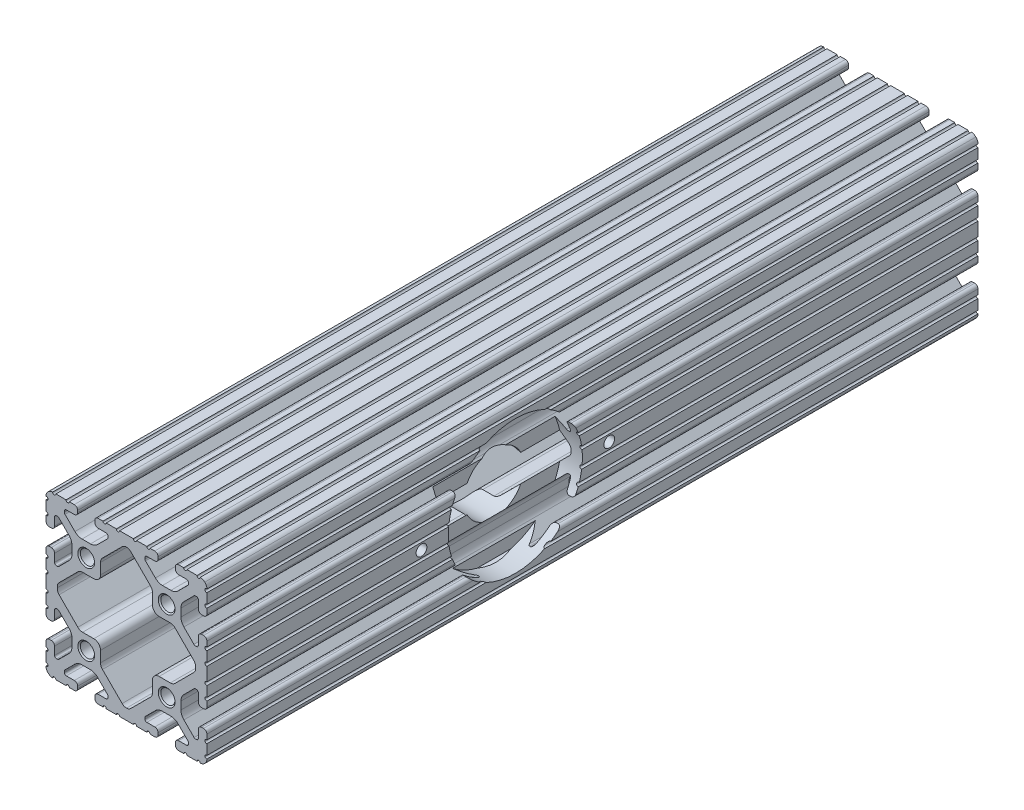
SolidWorks part; units mm, degrees
material "6061-T6 (SS)"
ref_plane "Front Plane" through (0, 0, 0) normal (0, 0, 1) x (1, 0, 0)
ref_plane "Top Plane" through (0, 0, 0) normal (0, 1, 0) x (1, 0, 0)
ref_plane "Right Plane" through (0, 0, 0) normal (1, 0, 0) x (0, 0, -1)
ref_plane "Plane1" through (0, 0, -254) normal (0, 0, -1) x (-1, 0, 0)
sketch "Sketch1" plane through (0, 0, -254) normal (0, 0, -1) x (-1, 0, 0)
  line L0 (31.9021, -2.4756) -> (23.0141, -11.3637)
  line L1 (20.769, -12.2936) -> (15.4686, -12.2936)
  line L2 (12.2936, -15.4686) -> (12.2936, -20.5983)
  line L3 (11.3637, -22.8433) -> (2.0515, -32.1555)
  line L4 (-2.0515, -32.1555) -> (-11.3637, -22.8433)
  line L5 (-12.2936, -20.5983) -> (-12.2936, -15.4686)
  line L6 (-15.4686, -12.2936) -> (-20.769, -12.2936)
  line L7 (-23.0141, -11.3637) -> (-31.9021, -2.4756)
  line L8 (-31.9021, 2.4756) -> (-23.0141, 11.3637)
  line L9 (-20.769, 12.2936) -> (-15.4686, 12.2936)
  line L10 (-12.2936, 15.4686) -> (-12.2936, 20.5983)
  line L11 (-11.3637, 22.8433) -> (-2.0515, 32.1555)
  line L12 (2.0515, 32.1555) -> (11.3637, 22.8433)
  line L13 (12.2936, 20.5983) -> (12.2936, 15.4686)
  line L14 (15.4686, 12.2936) -> (20.769, 12.2936)
  line L15 (23.0141, 11.3637) -> (31.9021, 2.4756)
  line L16 (36.5252, -23.0554) -> (35.6108, -23.0554)
  line L17 (34.036, -24.6302) -> (34.036, -28.448)
  line L18 (33.147, -29.337) -> (32.6643, -29.337)
  line L19 (32.0357, -29.0766) -> (27.1976, -24.2385)
  line L20 (25.8064, -20.8799) -> (25.8064, -17.2201)
  line L21 (27.1976, -13.8615) -> (31.9489, -9.1101)
  line L22 (32.7869, -8.763) -> (33.0603, -8.763)
  line L23 (34.036, -9.7387) -> (34.036, -13.4698)
  line L24 (35.6108, -15.0446) -> (36.5252, -15.0446)
  line L25 (38.1, -13.4698) -> (38.1, -11.075)
  line L26 (38.1, -9.552) -> (38.1, -4.7238)
  line L27 (38.1, -3.2007) -> (38.1, 3.2007)
  line L28 (38.1, 4.7238) -> (38.1, 9.552)
  line L29 (38.1, 11.075) -> (38.1, 13.4698)
  line L30 (36.5252, 15.0446) -> (35.6108, 15.0446)
  line L31 (34.036, 13.4698) -> (34.036, 9.7387)
  line L32 (33.0603, 8.763) -> (32.7869, 8.763)
  line L33 (31.9489, 9.1101) -> (27.1976, 13.8615)
  line L34 (25.8064, 17.2201) -> (25.8064, 20.8799)
  line L35 (27.1976, 24.2385) -> (32.0357, 29.0766)
  line L36 (32.6643, 29.337) -> (33.147, 29.337)
  line L37 (34.036, 28.448) -> (34.036, 24.6302)
  line L38 (35.6108, 23.0554) -> (36.5252, 23.0554)
  line L39 (38.1, 24.6302) -> (38.1, 27.0238)
  line L40 (38.1, 28.5453) -> (38.1, 33.373)
  line L41 (33.4288, 38.1) -> (28.6011, 38.1)
  line L42 (27.0772, 38.1) -> (24.6888, 38.1)
  line L43 (23.114, 36.5252) -> (23.114, 35.6108)
  line L44 (24.6888, 34.036) -> (28.448, 34.036)
  line L45 (29.337, 33.147) -> (29.337, 32.7207)
  line L46 (29.1002, 31.8885) -> (24.4093, 27.1976)
  line L47 (21.0507, 25.8064) -> (17.0493, 25.8064)
  line L48 (13.6907, 27.1976) -> (9.0234, 31.8649)
  line L49 (8.763, 32.4935) -> (8.763, 33.147)
  line L50 (9.652, 34.036) -> (13.4112, 34.036)
  line L51 (14.986, 35.6108) -> (14.986, 36.5252)
  line L52 (13.4112, 38.1) -> (11.1289, 38.1)
  line L53 (9.6053, 38.1) -> (4.7773, 38.1)
  line L54 (3.2537, 38.1) -> (-3.2537, 38.1)
  line L55 (-4.7773, 38.1) -> (-9.6053, 38.1)
  line L56 (-11.1289, 38.1) -> (-13.4112, 38.1)
  line L57 (-14.986, 36.5252) -> (-14.986, 35.6108)
  line L58 (-13.4112, 34.036) -> (-9.652, 34.036)
  line L59 (-8.763, 33.147) -> (-8.763, 32.4935)
  line L60 (-9.0234, 31.8649) -> (-13.6907, 27.1976)
  line L61 (-17.0493, 25.8064) -> (-21.0507, 25.8064)
  line L62 (-24.4093, 27.1976) -> (-29.1002, 31.8885)
  line L63 (-29.337, 32.7207) -> (-29.337, 33.147)
  line L64 (-28.448, 34.036) -> (-24.6888, 34.036)
  line L65 (-23.114, 35.6108) -> (-23.114, 36.5252)
  line L66 (-24.6888, 38.1) -> (-27.0772, 38.1)
  line L67 (-28.6011, 38.1) -> (-33.4288, 38.1)
  line L68 (-38.1, 33.373) -> (-38.1, 28.5453)
  line L69 (-38.1, 27.0238) -> (-38.1, 24.6302)
  line L70 (-36.5252, 23.0554) -> (-35.6108, 23.0554)
  line L71 (-34.036, 24.6302) -> (-34.036, 28.448)
  line L72 (-33.147, 29.337) -> (-32.6643, 29.337)
  line L73 (-32.0357, 29.0766) -> (-27.1976, 24.2385)
  line L74 (-25.8064, 20.8799) -> (-25.8064, 17.2201)
  line L75 (-27.1976, 13.8615) -> (-31.9489, 9.1101)
  line L76 (-32.7869, 8.763) -> (-33.0603, 8.763)
  line L77 (-34.036, 9.7387) -> (-34.036, 13.4698)
  line L78 (-35.6108, 15.0446) -> (-36.5252, 15.0446)
  line L79 (-38.1, 13.4698) -> (-38.1, 11.075)
  line L80 (-38.1, 9.552) -> (-38.1, 4.7238)
  line L81 (-38.1, 3.2007) -> (-38.1, -3.2007)
  line L82 (-38.1, -4.7238) -> (-38.1, -9.552)
  line L83 (-38.1, -11.075) -> (-38.1, -13.4698)
  line L84 (-36.5252, -15.0446) -> (-35.6108, -15.0446)
  line L85 (-34.036, -13.4698) -> (-34.036, -9.7387)
  line L86 (-33.0603, -8.763) -> (-32.7869, -8.763)
  line L87 (-31.9489, -9.1101) -> (-27.1976, -13.8615)
  line L88 (-25.8064, -17.2201) -> (-25.8064, -20.8799)
  line L89 (-27.1976, -24.2385) -> (-32.0357, -29.0766)
  line L90 (-32.6643, -29.337) -> (-33.147, -29.337)
  line L91 (-34.036, -28.448) -> (-34.036, -24.6302)
  line L92 (-35.6108, -23.0554) -> (-36.5252, -23.0554)
  line L93 (-38.1, -24.6302) -> (-38.1, -27.0238)
  line L94 (-38.1, -28.5453) -> (-38.1, -33.373)
  line L95 (-33.4288, -38.1) -> (-28.6011, -38.1)
  line L96 (-27.0772, -38.1) -> (-24.6888, -38.1)
  line L97 (-23.114, -36.5252) -> (-23.114, -35.6108)
  line L98 (-24.6888, -34.036) -> (-28.448, -34.036)
  line L99 (-29.337, -33.147) -> (-29.337, -32.7207)
  line L100 (-29.1002, -31.8885) -> (-24.4093, -27.1976)
  line L101 (-21.0507, -25.8064) -> (-17.0493, -25.8064)
  line L102 (-13.6907, -27.1976) -> (-9.0234, -31.8649)
  line L103 (-8.763, -32.4935) -> (-8.763, -33.147)
  line L104 (-9.652, -34.036) -> (-13.4112, -34.036)
  line L105 (-14.986, -35.6108) -> (-14.986, -36.5252)
  line L106 (-13.4112, -38.1) -> (-11.1289, -38.1)
  line L107 (-9.6053, -38.1) -> (-4.7773, -38.1)
  line L108 (-3.2537, -38.1) -> (3.2537, -38.1)
  line L109 (4.7773, -38.1) -> (9.6053, -38.1)
  line L110 (11.1289, -38.1) -> (13.4112, -38.1)
  line L111 (14.986, -36.5252) -> (14.986, -35.6108)
  line L112 (13.4112, -34.036) -> (9.652, -34.036)
  line L113 (8.763, -33.147) -> (8.763, -32.4935)
  line L114 (9.0234, -31.8649) -> (13.6907, -27.1976)
  line L115 (17.0493, -25.8064) -> (21.0507, -25.8064)
  line L116 (24.4093, -27.1976) -> (29.1002, -31.8885)
  line L117 (29.337, -32.7207) -> (29.337, -33.147)
  line L118 (28.448, -34.036) -> (24.6888, -34.036)
  line L119 (23.114, -35.6108) -> (23.114, -36.5252)
  line L120 (24.6888, -38.1) -> (27.0772, -38.1)
  line L121 (28.6011, -38.1) -> (33.4288, -38.1)
  line L122 (38.1, -33.373) -> (38.1, -28.5453)
  line L123 (38.1, -27.0238) -> (38.1, -24.6302)
  arc A0 (31.9021, 2.4756) -> (32.7287, 0) centre (29.8367, 0.4102) cw
  arc A1 (32.7287, 0) -> (31.9021, -2.4756) centre (29.8367, -0.4102) cw
  arc A2 (23.0141, -11.3637) -> (20.769, -12.2936) centre (20.769, -9.1186) cw
  arc A3 (15.4686, -12.2936) -> (12.2936, -15.4686) centre (15.4686, -15.4686) ccw
  arc A4 (12.2936, -20.5983) -> (11.3637, -22.8433) centre (9.1186, -20.5983) cw
  arc A5 (2.0515, -32.1555) -> (0, -33.011) centre (-0.0139, -30.09) cw
  arc A6 (0, -33.011) -> (-2.0515, -32.1555) centre (0.0139, -30.09) cw
  arc A7 (-11.3637, -22.8433) -> (-12.2936, -20.5983) centre (-9.1186, -20.5983) cw
  arc A8 (-12.2936, -15.4686) -> (-15.4686, -12.2936) centre (-15.4686, -15.4686) ccw
  arc A9 (-20.769, -12.2936) -> (-23.0141, -11.3637) centre (-20.769, -9.1186) cw
  arc A10 (-31.9021, -2.4756) -> (-32.7287, 0) centre (-29.8367, -0.4102) cw
  arc A11 (-32.7287, 0) -> (-31.9021, 2.4756) centre (-29.8367, 0.4102) cw
  arc A12 (-23.0141, 11.3637) -> (-20.769, 12.2936) centre (-20.769, 9.1186) cw
  arc A13 (-15.4686, 12.2936) -> (-12.2936, 15.4686) centre (-15.4686, 15.4686) ccw
  arc A14 (-12.2936, 20.5983) -> (-11.3637, 22.8433) centre (-9.1186, 20.5983) cw
  arc A15 (-2.0515, 32.1555) -> (0, 33.011) centre (0.0139, 30.09) cw
  arc A16 (0, 33.011) -> (2.0515, 32.1555) centre (-0.0139, 30.09) cw
  arc A17 (11.3637, 22.8433) -> (12.2936, 20.5983) centre (9.1186, 20.5983) cw
  arc A18 (12.2936, 15.4686) -> (15.4686, 12.2936) centre (15.4686, 15.4686) ccw
  arc A19 (20.769, 12.2936) -> (23.0141, 11.3637) centre (20.769, 9.1186) cw
  circle A20 centre (19.05, -19.05) radius 3.3274
  circle A21 centre (19.05, 19.05) radius 3.3274
  circle A22 centre (-19.05, 19.05) radius 3.3274
  circle A23 centre (-19.05, -19.05) radius 3.3274
  arc A24 (38.1, -24.6302) -> (36.5252, -23.0554) centre (36.5252, -24.6302) ccw
  arc A25 (35.6108, -23.0554) -> (34.036, -24.6302) centre (35.6108, -24.6302) ccw
  arc A26 (34.036, -28.448) -> (33.147, -29.337) centre (33.147, -28.448) cw
  arc A27 (32.6643, -29.337) -> (32.0357, -29.0766) centre (32.6643, -28.448) cw
  arc A28 (27.1976, -24.2385) -> (25.8064, -20.8799) centre (30.5562, -20.8799) cw
  arc A29 (25.8064, -17.2201) -> (27.1976, -13.8615) centre (30.5562, -17.2201) cw
  arc A30 (31.9489, -9.1101) -> (32.7869, -8.763) centre (32.7869, -9.9481) cw
  arc A31 (33.0603, -8.763) -> (34.036, -9.7387) centre (33.0603, -9.7387) cw
  arc A32 (34.036, -13.4698) -> (35.6108, -15.0446) centre (35.6108, -13.4698) ccw
  arc A33 (36.5252, -15.0446) -> (38.1, -13.4698) centre (36.5252, -13.4698) ccw
  arc A34 (38.1, -11.075) -> (38.1, -9.552) centre (37.9035, -10.3135) cw
  arc A35 (38.1, -4.7238) -> (38.1, -3.2007) centre (37.9035, -3.9622) cw
  arc A36 (38.1, 3.2007) -> (38.1, 4.7238) centre (37.9035, 3.9622) cw
  arc A37 (38.1, 9.552) -> (38.1, 11.075) centre (37.9035, 10.3135) cw
  arc A38 (38.1, 13.4698) -> (36.5252, 15.0446) centre (36.5252, 13.4698) ccw
  arc A39 (35.6108, 15.0446) -> (34.036, 13.4698) centre (35.6108, 13.4698) ccw
  arc A40 (34.036, 9.7387) -> (33.0603, 8.763) centre (33.0603, 9.7387) cw
  arc A41 (32.7869, 8.763) -> (31.9489, 9.1101) centre (32.7869, 9.9481) cw
  arc A42 (27.1976, 13.8615) -> (25.8064, 17.2201) centre (30.5562, 17.2201) cw
  arc A43 (25.8064, 20.8799) -> (27.1976, 24.2385) centre (30.5562, 20.8799) cw
  arc A44 (32.0357, 29.0766) -> (32.6643, 29.337) centre (32.6643, 28.448) cw
  arc A45 (33.147, 29.337) -> (34.036, 28.448) centre (33.147, 28.448) cw
  arc A46 (34.036, 24.6302) -> (35.6108, 23.0554) centre (35.6108, 24.6302) ccw
  arc A47 (36.5252, 23.0554) -> (38.1, 24.6302) centre (36.5252, 24.6302) ccw
  arc A48 (38.1, 27.0238) -> (38.1, 28.5453) centre (37.9035, 27.7845) cw
  arc A49 (38.1, 33.373) -> (38.1, 34.8455) centre (37.9035, 34.1092) cw
  arc A50 (38.1, 34.8455) -> (37.0861, 37.1826) centre (34.925, 34.8566) ccw
  arc A51 (37.0861, 37.1826) -> (34.9527, 38.1) centre (34.8521, 34.9266) ccw
  arc A52 (34.9527, 38.1) -> (33.4288, 38.1) centre (34.1907, 38.0824) cw
  arc A53 (28.6011, 38.1) -> (27.0772, 38.1) centre (27.8392, 38.0824) cw
  arc A54 (24.6888, 38.1) -> (23.114, 36.5252) centre (24.6888, 36.5252) ccw
  arc A55 (23.114, 35.6108) -> (24.6888, 34.036) centre (24.6888, 35.6108) ccw
  arc A56 (28.448, 34.036) -> (29.337, 33.147) centre (28.448, 33.147) cw
  arc A57 (29.337, 32.7207) -> (29.1002, 31.8885) centre (28.4716, 32.5172) cw
  arc A58 (24.4093, 27.1976) -> (21.0507, 25.8064) centre (21.0507, 30.5562) cw
  arc A59 (17.0493, 25.8064) -> (13.6907, 27.1976) centre (17.0493, 30.5562) cw
  arc A60 (9.0234, 31.8649) -> (8.763, 32.4935) centre (9.652, 32.4935) cw
  arc A61 (8.763, 33.147) -> (9.652, 34.036) centre (9.652, 33.147) cw
  arc A62 (13.4112, 34.036) -> (14.986, 35.6108) centre (13.4112, 35.6108) ccw
  arc A63 (14.986, 36.5252) -> (13.4112, 38.1) centre (13.4112, 36.5252) ccw
  arc A64 (11.1289, 38.1) -> (9.6053, 38.1) centre (10.3671, 38.0824) cw
  arc A65 (4.7773, 38.1) -> (3.2537, 38.1) centre (4.0155, 38.0824) cw
  arc A66 (-3.2537, 38.1) -> (-4.7773, 38.1) centre (-4.0155, 38.0824) cw
  arc A67 (-9.6053, 38.1) -> (-11.1289, 38.1) centre (-10.3671, 38.0824) cw
  arc A68 (-13.4112, 38.1) -> (-14.986, 36.5252) centre (-13.4112, 36.5252) ccw
  arc A69 (-14.986, 35.6108) -> (-13.4112, 34.036) centre (-13.4112, 35.6108) ccw
  arc A70 (-9.652, 34.036) -> (-8.763, 33.147) centre (-9.652, 33.147) cw
  arc A71 (-8.763, 32.4935) -> (-9.0234, 31.8649) centre (-9.652, 32.4935) cw
  arc A72 (-13.6907, 27.1976) -> (-17.0493, 25.8064) centre (-17.0493, 30.5562) cw
  arc A73 (-21.0507, 25.8064) -> (-24.4093, 27.1976) centre (-21.0507, 30.5562) cw
  arc A74 (-29.1002, 31.8885) -> (-29.337, 32.7207) centre (-28.4716, 32.5172) cw
  arc A75 (-29.337, 33.147) -> (-28.448, 34.036) centre (-28.448, 33.147) cw
  arc A76 (-24.6888, 34.036) -> (-23.114, 35.6108) centre (-24.6888, 35.6108) ccw
  arc A77 (-23.114, 36.5252) -> (-24.6888, 38.1) centre (-24.6888, 36.5252) ccw
  arc A78 (-27.0772, 38.1) -> (-28.6011, 38.1) centre (-27.8392, 38.0824) cw
  arc A79 (-33.4288, 38.1) -> (-34.9527, 38.1) centre (-34.1907, 38.0824) cw
  arc A80 (-34.9527, 38.1) -> (-37.0861, 37.1826) centre (-34.8521, 34.9266) ccw
  arc A81 (-37.0861, 37.1826) -> (-38.1, 34.8455) centre (-34.925, 34.8566) ccw
  arc A82 (-38.1, 34.8455) -> (-38.1, 33.373) centre (-37.9035, 34.1092) cw
  arc A83 (-38.1, 28.5453) -> (-38.1, 27.0238) centre (-37.9035, 27.7845) cw
  arc A84 (-38.1, 24.6302) -> (-36.5252, 23.0554) centre (-36.5252, 24.6302) ccw
  arc A85 (-35.6108, 23.0554) -> (-34.036, 24.6302) centre (-35.6108, 24.6302) ccw
  arc A86 (-34.036, 28.448) -> (-33.147, 29.337) centre (-33.147, 28.448) cw
  arc A87 (-32.6643, 29.337) -> (-32.0357, 29.0766) centre (-32.6643, 28.448) cw
  arc A88 (-27.1976, 24.2385) -> (-25.8064, 20.8799) centre (-30.5562, 20.8799) cw
  arc A89 (-25.8064, 17.2201) -> (-27.1976, 13.8615) centre (-30.5562, 17.2201) cw
  arc A90 (-31.9489, 9.1101) -> (-32.7869, 8.763) centre (-32.7869, 9.9481) cw
  arc A91 (-33.0603, 8.763) -> (-34.036, 9.7387) centre (-33.0603, 9.7387) cw
  arc A92 (-34.036, 13.4698) -> (-35.6108, 15.0446) centre (-35.6108, 13.4698) ccw
  arc A93 (-36.5252, 15.0446) -> (-38.1, 13.4698) centre (-36.5252, 13.4698) ccw
  arc A94 (-38.1, 11.075) -> (-38.1, 9.552) centre (-37.9035, 10.3135) cw
  arc A95 (-38.1, 4.7238) -> (-38.1, 3.2007) centre (-37.9035, 3.9622) cw
  arc A96 (-38.1, -3.2007) -> (-38.1, -4.7238) centre (-37.9035, -3.9622) cw
  arc A97 (-38.1, -9.552) -> (-38.1, -11.075) centre (-37.9035, -10.3135) cw
  arc A98 (-38.1, -13.4698) -> (-36.5252, -15.0446) centre (-36.5252, -13.4698) ccw
  arc A99 (-35.6108, -15.0446) -> (-34.036, -13.4698) centre (-35.6108, -13.4698) ccw
  arc A100 (-34.036, -9.7387) -> (-33.0603, -8.763) centre (-33.0603, -9.7387) cw
  arc A101 (-32.7869, -8.763) -> (-31.9489, -9.1101) centre (-32.7869, -9.9481) cw
  arc A102 (-27.1976, -13.8615) -> (-25.8064, -17.2201) centre (-30.5562, -17.2201) cw
  arc A103 (-25.8064, -20.8799) -> (-27.1976, -24.2385) centre (-30.5562, -20.8799) cw
  arc A104 (-32.0357, -29.0766) -> (-32.6643, -29.337) centre (-32.6643, -28.448) cw
  arc A105 (-33.147, -29.337) -> (-34.036, -28.448) centre (-33.147, -28.448) cw
  arc A106 (-34.036, -24.6302) -> (-35.6108, -23.0554) centre (-35.6108, -24.6302) ccw
  arc A107 (-36.5252, -23.0554) -> (-38.1, -24.6302) centre (-36.5252, -24.6302) ccw
  arc A108 (-38.1, -27.0238) -> (-38.1, -28.5453) centre (-37.9035, -27.7845) cw
  arc A109 (-38.1, -33.373) -> (-38.1, -34.8455) centre (-37.9035, -34.1092) cw
  arc A110 (-38.1, -34.8455) -> (-37.0861, -37.1826) centre (-34.925, -34.8566) ccw
  arc A111 (-37.0861, -37.1826) -> (-34.9527, -38.1) centre (-34.8521, -34.9266) ccw
  arc A112 (-34.9527, -38.1) -> (-33.4288, -38.1) centre (-34.1907, -38.0824) cw
  arc A113 (-28.6011, -38.1) -> (-27.0772, -38.1) centre (-27.8392, -38.0824) cw
  arc A114 (-24.6888, -38.1) -> (-23.114, -36.5252) centre (-24.6888, -36.5252) ccw
  arc A115 (-23.114, -35.6108) -> (-24.6888, -34.036) centre (-24.6888, -35.6108) ccw
  arc A116 (-28.448, -34.036) -> (-29.337, -33.147) centre (-28.448, -33.147) cw
  arc A117 (-29.337, -32.7207) -> (-29.1002, -31.8885) centre (-28.4716, -32.5172) cw
  arc A118 (-24.4093, -27.1976) -> (-21.0507, -25.8064) centre (-21.0507, -30.5562) cw
  arc A119 (-17.0493, -25.8064) -> (-13.6907, -27.1976) centre (-17.0493, -30.5562) cw
  arc A120 (-9.0234, -31.8649) -> (-8.763, -32.4935) centre (-9.652, -32.4935) cw
  arc A121 (-8.763, -33.147) -> (-9.652, -34.036) centre (-9.652, -33.147) cw
  arc A122 (-13.4112, -34.036) -> (-14.986, -35.6108) centre (-13.4112, -35.6108) ccw
  arc A123 (-14.986, -36.5252) -> (-13.4112, -38.1) centre (-13.4112, -36.5252) ccw
  arc A124 (-11.1289, -38.1) -> (-9.6053, -38.1) centre (-10.3671, -38.0824) cw
  arc A125 (-4.7773, -38.1) -> (-3.2537, -38.1) centre (-4.0155, -38.0824) cw
  arc A126 (3.2537, -38.1) -> (4.7773, -38.1) centre (4.0155, -38.0824) cw
  arc A127 (9.6053, -38.1) -> (11.1289, -38.1) centre (10.3671, -38.0824) cw
  arc A128 (13.4112, -38.1) -> (14.986, -36.5252) centre (13.4112, -36.5252) ccw
  arc A129 (14.986, -35.6108) -> (13.4112, -34.036) centre (13.4112, -35.6108) ccw
  arc A130 (9.652, -34.036) -> (8.763, -33.147) centre (9.652, -33.147) cw
  arc A131 (8.763, -32.4935) -> (9.0234, -31.8649) centre (9.652, -32.4935) cw
  arc A132 (13.6907, -27.1976) -> (17.0493, -25.8064) centre (17.0493, -30.5562) cw
  arc A133 (21.0507, -25.8064) -> (24.4093, -27.1976) centre (21.0507, -30.5562) cw
  arc A134 (29.1002, -31.8885) -> (29.337, -32.7207) centre (28.4716, -32.5172) cw
  arc A135 (29.337, -33.147) -> (28.448, -34.036) centre (28.448, -33.147) cw
  arc A136 (24.6888, -34.036) -> (23.114, -35.6108) centre (24.6888, -35.6108) ccw
  arc A137 (23.114, -36.5252) -> (24.6888, -38.1) centre (24.6888, -36.5252) ccw
  arc A138 (27.0772, -38.1) -> (28.6011, -38.1) centre (27.8392, -38.0824) cw
  arc A139 (33.4288, -38.1) -> (34.9527, -38.1) centre (34.1907, -38.0824) cw
  arc A140 (34.9527, -38.1) -> (37.0861, -37.1826) centre (34.8521, -34.9266) ccw
  arc A141 (37.0861, -37.1826) -> (38.1, -34.8455) centre (34.925, -34.8566) ccw
  arc A142 (38.1, -34.8455) -> (38.1, -33.373) centre (37.9035, -34.1092) cw
  arc A143 (38.1, -28.5453) -> (38.1, -27.0238) centre (37.9035, -27.7845) cw
extrude "Boss-Extrude1" add sketch "Sketch1" against normal blind 365.125
sketch "Sketch2" plane through (-38.1, 0, 0) normal (-1, 0, 0) x (0, 0, 1)
  line L1 (111.125, 38.1) -> (-254, 38.1) construction
  line L2 (-254, -3.2007) -> (-254, 3.2007) construction
  circle A0 centre (-35.925, 0) radius 31.75
  point P4 (-254, 0)
  dimension "D1" = 63.5
  dimension "D2" = 218.075
  dimension "D3" = 38.1
extrude "Cut-Extrude1" cut sketch "Sketch2" against normal blind 10.16
sketch "Sketch3" plane through (-38.1, 0, 0) normal (-1, 0, 0) x (0, 0, 1)
  line L1 (-254, -3.2007) -> (-254, 3.2007) construction
  circle A0 centre (-34.925, 0) radius 14.25
  dimension "D1" = 28.5
  dimension "D2" = 219.075
  dimension "D3" = 38.1
extrude "Cut-Extrude2" cut sketch "Sketch3" against normal through all
sketch "Sketch4" plane through (38.1, 0, 0) normal (1, 0, 0) x (0, 0, -1)
  circle A0 centre (34.925, 0) radius 31.75
  arc A3 (39.5755, 13.4698) -> (30.2745, 13.4698) centre (34.925, 0) ccw construction
  dimension "D1" = 0
  dimension "D2" = 63.5
extrude "Cut-Extrude3" cut sketch "Sketch4" against normal blind 10.16
hole_wizard "1/4-20 Tapped Hole1" positions "Sketch5" profile "Sketch6" tap size "1/4-20" standard "ANSI Inch" end condition through all
sketch "Sketch5" plane through (38.1, 0, 0) normal (1, 0, 0) x (0, 0, -1)
  arc A0 (48.8257, 28.5453) -> (21.0243, 28.5453) centre (34.925, 0) ccw construction
  point P0 (-9.525, 0)
  point P7 (34.925, 31.75)
  dimension "D1" = 44.45
cosmetic thread "Hole Thread1" parameters "D2"=6.35
sketch "Sketch6" plane through (38.1, 0, 9.525) normal (0, 1, 0) x (0, 0, -1)
  line L0 (0, 0) -> (0, 76.2)
  line L1 (0, 76.2) -> (2.5527, 76.2)
  line L2 (2.5527, 76.2) -> (2.5527, 0)
  line L5 (2.5527, 0) -> (0, 0)
  line L11 (0, -6.35) -> (0, 107.95) construction
  dimension "Thru Tap Drill Dia." = 5.1054
  dimension "Thru Tap Drill Depth" = 76.2
pattern_circular "CirPattern1" count 2 over 360 about axis through (38.1, 0, -34.925) along (1, 0, 0) of "1/4-20 Tapped Hole1"
hole_wizard "5/16-18 Tapped Hole1" positions "Sketch7" profile "Sketch8" tap size "5/16-18" standard "ANSI Inch"
sketch "Sketch7" plane through (0, 0, 111.125) normal (0, 0, 1) x (1, 0, 0)
  point P0 (19.05, -19.05)
  point P3 (-19.05, -19.05)
  point P6 (-19.05, 19.05)
  point P9 (19.05, 19.05)
sketch "Sketch8" plane through (19.05, -19.05, 111.125) normal (1, 0, 0) x (0, -1, 0)
  line L0 (0, 0) -> (0, 22.0711)
  line L1 (0, 22.0711) -> (3.2639, 20.11)
  line L2 (3.2639, 20.11) -> (3.2639, 0.5914)
  line L3 (3.2639, 0.5914) -> (3.9688, 0)
  line L5 (3.9688, 0) -> (0, 0)
  line L6 (-3.2639, 0.5914) -> (-3.9688, 0) construction
  line L10 (0, 22.0711) -> (-3.2639, 20.11) construction
  line L11 (0, -6.35) -> (0, 107.95) construction
  dimension "Tap Drill Dia." = 6.5278
  dimension "Tap Drill Depth" = 20.11
  dimension "Near C'Sink Dia." = 7.9375
  dimension "Near C'Sink Angle" = 100
  dimension "Drill Angle" = 118
hole_wizard "1/4-20 Tapped Hole3" positions "Sketch11" profile "Sketch12" tap size "1/4-20" standard "ANSI Inch" end condition through all
sketch "Sketch11" plane through (38.1, 0, 0) normal (1, 0, 0) x (0, 0, -1)
  circle A0 centre (-9.525, 0) radius 2.5527 construction
  arc A1 (42.9146, -30.7283) -> (54.5213, -24.9809) centre (34.925, 0) ccw construction
  point P0 (-5.2359, 19.05)
  dimension "D2" = 44.45
  dimension "D1" = 19.05
sketch "Sketch12" plane through (38.1, 19.05, 5.2359) normal (0, 1, 0) x (0, 0, -1)
  line L0 (0, 0) -> (0, 76.2)
  line L1 (0, 76.2) -> (2.5527, 76.2)
  line L2 (2.5527, 76.2) -> (2.5527, 0)
  line L5 (2.5527, 0) -> (0, 0)
  line L11 (0, -6.35) -> (0, 107.95) construction
  dimension "Thru Tap Drill Dia." = 5.1054
  dimension "Thru Tap Drill Depth" = 76.2
cosmetic thread "Hole Thread5" parameters "D2"=6.35
pattern_linear "LPattern2" count 2 spacing 80.3219 along (0, 0, -1) count 2 spacing 38.1 along (0, -1, 0) of "1/4-20 Tapped Hole3"
